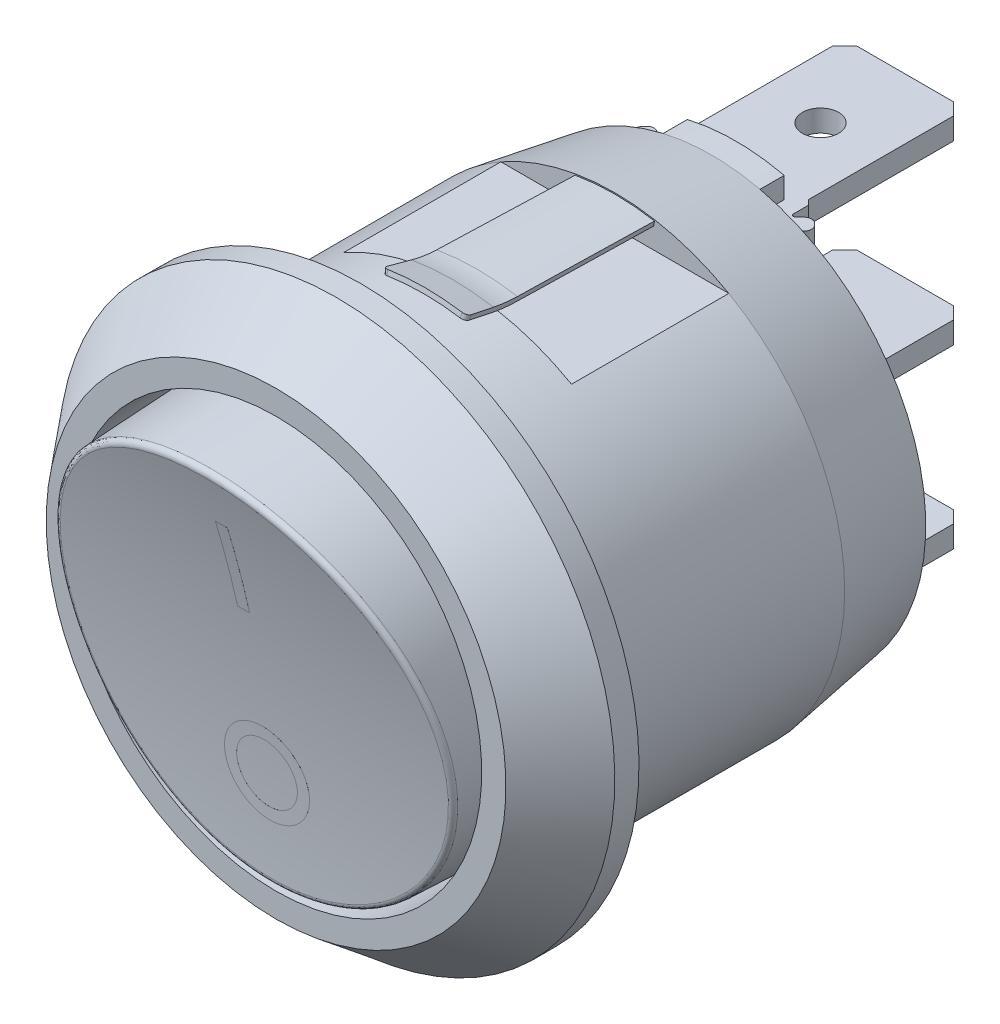
SolidWorks part; units mm, degrees
material "PE Baixa/Média Densidade"
ref_plane "Plano frontal" through (0, 0, 0) normal (0, 0, 1) x (1, 0, 0)
ref_plane "Plano superior" through (0, 0, 0) normal (0, 1, 0) x (1, 0, 0)
ref_plane "Plano direito" through (0, 0, 0) normal (1, 0, 0) x (0, 0, -1)
sketch "Esboço1" plane through (0, 0, 0) normal (1, 0, 0) x (0, 0, -1)
  line L0 (0, 0) -> (-18, 0) construction
  line L1 (0, 0) -> (0, 8.85)
  line L2 (0, 8.85) -> (-4, 9.5)
  line L3 (-4, 9.5) -> (-14.5, 9.5)
  line L4 (-14.5, 9.5) -> (-14.5, 11.5)
  line L5 (-14.5, 11.5) -> (-15.5, 11.5)
  line L6 (-15.5, 11.5) -> (-18, 9.5)
  line L7 (-18, 9.5) -> (-18, 8.5)
  line L8 (-18, 8.5) -> (-12.5, 8.5)
  line L9 (-12.5, 8.5) -> (-12.5, 0)
  line L10 (0, 0) -> (-12.5, 0)
  dimension "D1" = 18
  dimension "D2" = 17.7
  dimension "D3" = 14.5
  dimension "D4" = 19
  dimension "D5" = 4
  dimension "D6" = 23
  dimension "D7" = 1
  dimension "D8" = 17
  dimension "D9" = 5.5
revolve "Revolução1" add sketch "Esboço1" angle 360 about L0
sketch "Esboço2" plane through (0, 0, 0) normal (1, 0, 0) x (0, 0, -1)
  line L0 (-18, 0) -> (0, 0) construction
  line L1 (-18, 9.5) -> (-18, -9.5) construction
  line L2 (-12.6, 0) -> (-12.6, 8.4)
  line L3 (-12.6, 8.4) -> (-21, 8.4) construction
  line L4 (-21, 8) -> (-21, 0)
  line L5 (-12.5, 8.5) -> (-12.5, -8.5) construction
  line L6 (-12.5, 8.5) -> (-18, 8.5) construction
  line L7 (-12.6, 8.4) -> (-21, 8)
  line L8 (-21, 8.4) -> (-21, 8) construction
  line L9 (-12.6, 0) -> (-21, 0)
  dimension "D1" = 0.1
  dimension "D2" = 0.1
  dimension "D3" = 0.4
  dimension "D4" = 3
revolve "Revolução2" add sketch "Esboço2" angle 360 about L9
sketch "Esboço3" plane through (0, 0, 0) normal (1, 0, 0) x (0, 0, -1)
  line L0 (-21, -8) -> (-12.6, -8.4) construction
  line L1 (-21, 8) -> (-24.6303, 8)
  line L2 (-24.6303, 8) -> (-24.6303, -8.1333)
  line L3 (-24.6303, -8.1333) -> (-18.2, -8.1333)
  line L4 (-18.2, -8.1333) -> (-18.2, 9.4452) construction
  line L5 (-18, 9.5) -> (-18, -9.5) construction
  arc A0 (-21, 8) -> (-18.2, -8.1333) centre (-66.0794, -8.1333) cw
  dimension "D1" = 0.2
extrude "Corte-extrusão1" cut sketch "Esboço3" against normal mid plane 30
fillet "Filete1" radius 0.2 1 edges at (4.4558, 6.6703, 20.546)
ref_plane "Plano1" through (0, 0, 24.4108) normal (0, 0, 1) x (1, 0, 0)
surface "Superfície-Offset1" parameters "D1"=0.001
sketch "Esboço4" plane through (0, 0, 24.4108) normal (0, 0, 1) x (1, 0, 0)
  line L0 (-9.5, 0) -> (9.5, 0) construction
  line L1 (0, 0) -> (0, -4.0712) construction
  line L2 (0, -8.1424) -> (0, -4.0712) construction
  line L3 (0, 2.2564) -> (0, 0) construction
  line L4 (-0.25, 5.7564) -> (0.25, 5.7564)
  line L5 (-0.25, 5.7564) -> (-0.25, 2.2564)
  line L6 (-0.25, 2.2564) -> (0.25, 2.2564)
  line L7 (0.25, 5.7564) -> (0.25, 2.2564)
  line L8 (-0.25, 5.7564) -> (0.25, 2.2564) construction
  line L9 (-0.25, 2.2564) -> (0.25, 5.7564) construction
  line L10 (0, 8.0128) -> (0, 5.7564) construction
  circle A0 centre (0, 0) radius 9.5 construction
  circle A1 centre (0, -4.0712) radius 1.75
  circle A2 centre (0, -4.0712) radius 1.25
  spline S0 degree 3 poles (-6.2452, -5.2454) (-5.5004, -6.0245) (-5.0951, -6.3713) (-4.4399, -6.8293) (-4.2136, -6.9715) (-3.7446, -7.2346) (-3.5031, -7.3546) (-2.7693, -7.6754) (-2.2636, -7.8396) (-1.4801, -8.0112) (-1.2132, -8.0559) (-0.6804, -8.1183) (-0.4142, -8.1362) (0.3837, -8.1507) (0.9149, -8.1087) (1.9756, -7.9174) (2.4892, -7.7707) (3.2316, -7.478) (3.4746, -7.3682) (3.9514, -7.1236) (4.1859, -6.9882) (4.8603, -6.5528) (5.2764, -6.2217) (5.8507, -5.6643) (6.0346, -5.4674) (6.3811, -5.0568) (6.5427, -4.8445) (6.994, -4.1873) (7.2503, -3.7225) (7.566, -2.9842) (7.6591, -2.7325) (7.8183, -2.2264) (7.9516, -1.7155) (8.0342, -1.1948) (8.0912, -0.6694) (8.1069, -0.4027) (8.1142, 0.3918) (8.0672, 0.913) (7.922, 1.683) (7.8611, 1.9377) (7.7137, 2.4429) (7.6273, 2.6925) (7.3354, 3.4196) (7.0961, 3.8807) (6.5283, 4.7562) (6.1978, 5.1713) (5.4672, 5.9245) (5.0608, 6.269) (4.1959, 6.8677) (3.7366, 7.124) (3.0056, 7.4423) (2.754, 7.5375) (2.2474, 7.701) (1.7348, 7.8391) (1.2104, 7.9268) (0.68, 7.9888) (0.4102, 8.0069) (-0.3949, 8.0209) (-0.9246, 7.9776) (-1.9703, 7.7887) (-2.4915, 7.6403) (-3.4759, 7.2524) (-3.9436, 7.0131) (-4.6092, 6.5868) (-4.8261, 6.4323) (-5.2401, 6.1061) (-5.4374, 5.9342) (-6.0018, 5.3929) (-6.3413, 4.9981) (-6.7945, 4.3533) (-6.9352, 4.1308) (-7.1922, 3.677) (-7.4262, 3.2125) (-7.6148, 2.7267) (-7.7801, 2.2301) (-7.8515, 1.9749) (-8.0263, 1.2053) (-8.0918, 0.6862) (-8.1212, -0.3642) (-8.0835, -0.9002) (-7.9054, -1.9414) (-7.7661, -2.4509) (-7.4793, -3.1981) (-7.3703, -3.4446) (-7.1308, -3.9207) (-6.9999, -4.1516) (-6.5741, -4.8237) (-6.2452, -5.2454) (-5.5004, -6.0245) (-5.0951, -6.3713) knots -0.03125 -0.03125 0 0 0.03125 0.03125 0.046875 0.046875 0.0625 0.0625 0.09375 0.09375 0.109375 0.109375 0.125 0.125 0.15625 0.15625 0.1875 0.1875 0.203125 0.203125 0.21875 0.21875 0.25 0.25 0.265625 0.265625 0.28125 0.28125 0.3125 0.3125 0.328125 0.328125 0.34375 0.359375 0.359375 0.375 0.375 0.40625 0.40625 0.421875 0.421875 0.4375 0.4375 0.46875 0.46875 0.5 0.5 0.53125 0.53125 0.5625 0.5625 0.578125 0.578125 0.59375 0.609375 0.609375 0.625 0.625 0.65625 0.65625 0.6875 0.6875 0.71875 0.71875 0.734375 0.734375 0.75 0.75 0.78125 0.78125 0.796875 0.796875 0.8125 0.828125 0.828125 0.84375 0.84375 0.875 0.875 0.90625 0.90625 0.9375 0.9375 0.953125 0.953125 0.96875 0.96875 1 1 1.03125 1.03125 1.046875 only from (-5.8728, -5.6349) to (-5.8728, -5.6349) construction
  point P12 (0, 4.0064)
  dimension "D1" = 3.5
  dimension "D3" = 0.5
  dimension "D4" = 3.5
  dimension "D2" = 0.5
extrude "Ressalto-extrusão1" add sketch "Esboço4" against normal up to surface (6.0382 mm away) up to face at (5.0218, 5.9632, 20.3222)
other "Corte de superfície1" flip cut yes
sketch "Esboço5" plane through (0, 0, 0) normal (1, 0, 0) x (0, 0, -1)
  line L0 (-4, 8.25) -> (-4, -8.25) construction
  line L1 (-10.5, 11.4584) -> (-4, 11.4584)
  line L2 (-10.5, 11.4584) -> (-10.5, 8.25)
  line L3 (-10.5, 8.25) -> (-4, 8.25)
  line L4 (-4, 11.4584) -> (-4, 8.25)
  line L5 (-10.5, -11.4584) -> (-4, -11.4584)
  line L6 (-10.5, -11.4584) -> (-10.5, -8.25)
  line L7 (-10.5, -8.25) -> (-4, -8.25)
  line L8 (-4, -11.4584) -> (-4, -8.25)
  line L9 (0, 0) -> (-4, 0) construction
  line L10 (-4, 9.5) -> (-4, -9.5) construction
  dimension "D1" = 16.5
  dimension "D2" = 6.5
extrude "Corte-extrusão2" cut sketch "Esboço5" against normal mid plane 50
sketch "Esboço6" plane through (0, 0, 0) normal (1, 0, 0) x (0, 0, -1)
  line L0 (-4, 9.25) -> (-9.6985, 9.4121)
  line L2 (-4, 9.5) -> (-4, 8.25) construction
  line L3 (-10.7572, 9.5565) -> (-11.9, 9.8393)
  line L4 (-14.5, -11.5) -> (-14.5, 11.5) construction
  line L5 (-10.5, 8.25) -> (-4, 8.25) construction
  line L6 (-3.9943, 9.4499) -> (-9.6928, 9.6121)
  line L7 (-10.7092, 9.7506) -> (-11.852, 10.0334)
  line L8 (-11.852, 10.0334) -> (-11.9, 9.8393)
  line L9 (-3.9943, 9.4499) -> (-4, 9.25)
  line L10 (-4, 0) -> (-9.0622, 0) construction
  line L11 (-4, 8.25) -> (-4, -8.25) construction
  arc A0 (-9.6985, 9.4121) -> (-10.7572, 9.5565) centre (-9.5562, 14.4101) cw
  arc A1 (-9.6928, 9.6121) -> (-10.7092, 9.7506) centre (-9.5562, 14.4101) cw
  dimension "D2" = 5
  dimension "D1" = 2.6
  dimension "D3" = 1
  dimension "D4" = 0.2
revolve "Revolução4" add sketch "Esboço6" angle 20 mid plane about L10
fillet "Filete2" radius 0.2 2 edges at (-1.7254, 9.7854, 11.876) (1.7254, 9.7854, 11.876)
mirror "Espelhar1" about plane through (0, 0, 0) normal (0, 1, 0) of bodies 109
sketch "Esboço7" plane through (0, 0, 4) normal (0, 0, 1) x (1, 0, 0)
  line L0 (-9.4472, 1) -> (-10.4472, 1)
  line L1 (-10.4472, 1) -> (-10.4472, -1)
  line L2 (-10.4472, -1) -> (-9.4472, -1)
  circle A0 centre (0, 0) radius 9.5 construction
  arc A1 (-9.4472, 1) -> (-9.4472, -1) centre (0, 0) ccw
  dimension "D1" = 1
  dimension "D2" = 2
extrude "Ressalto-extrusão2" add sketch "Esboço7" along normal up to surface (10.5 mm away) up to face at (0, 11.5, 14.5)
sketch "Esboço8" plane through (0, 0, 0) normal (0, 0, -1) x (-1, 0, 0)
  line L0 (-2, 8.621) -> (-2, 7.75)
  line L1 (-2, 7.75) -> (2, 7.75)
  line L2 (2, 7.75) -> (2, 8.621)
  line L3 (0, 7.75) -> (0, 8.85) construction
  line L4 (-2, 6.85) -> (2, 6.85)
  line L5 (-2, 6.85) -> (-2, 5.75)
  line L6 (-2, 5.75) -> (2, 5.75)
  line L7 (2, 6.85) -> (2, 5.75)
  line L8 (0, 6.85) -> (0, 5.75) construction
  line L9 (0, -0.45) -> (0, 0.45) construction
  line L10 (-2, 1.55) -> (2, 1.55)
  line L11 (-2, 1.55) -> (-2, 0.45)
  line L12 (-2, 0.45) -> (2, 0.45)
  line L13 (2, 1.55) -> (2, 0.45)
  line L14 (-2, -0.45) -> (2, -0.45)
  line L15 (-2, -0.45) -> (-2, -1.55)
  line L16 (-2, -1.55) -> (2, -1.55)
  line L17 (2, -0.45) -> (2, -1.55)
  line L18 (0, 0) -> (8.85, 0) construction
  line L19 (2, -7.75) -> (2, -8.621)
  line L20 (-2, -8.621) -> (-2, -7.75)
  line L21 (-2, -7.75) -> (2, -7.75)
  line L22 (-2, -6.85) -> (-2, -5.75)
  line L23 (-2, -6.85) -> (2, -6.85)
  line L24 (2, -6.85) -> (2, -5.75)
  line L25 (-2, -5.75) -> (2, -5.75)
  circle A0 centre (0, 0) radius 8.85 construction
  arc A1 (2, 8.621) -> (-2, 8.621) centre (0, 0) ccw
  arc A2 (2, -8.621) -> (-2, -8.621) centre (0, 0) cw
  dimension "D1" = 4
  dimension "D2" = 0.9
  dimension "D3" = 3.1
  dimension "D4" = 0.9
extrude "Ressalto-extrusão3" add sketch "Esboço8" along normal blind 1
sketch "Esboço9" plane through (0, -7.75, 0) normal (0, 1, 0) x (1, 0, 0)
  line L0 (2, 0) -> (3.245, 0)
  line L1 (8.85, 0) -> (2, 0) construction
  line L2 (3.245, 0) -> (3.5379, 0.2929)
  line L3 (3.5379, 0.7172) -> (3.4672, 0.7879)
  line L4 (3.0429, 0.7879) -> (2.8707, 0.6157)
  line L5 (2.7, 0.6864) -> (2.7, 1.3)
  line L6 (2.7, 1.3) -> (2.5, 1.5)
  line L7 (2.5, 1.5) -> (2.5, 7.5)
  line L8 (2.5, 7.5) -> (2, 8)
  line L9 (2, 8) -> (-2, 8)
  line L10 (0, 8) -> (0, 0) construction
  line L11 (-2, 0) -> (2, 0) construction
  line L12 (2, 1) -> (-2, 1) construction
  line L13 (-2, 0) -> (-8.85, 0) construction
  line L14 (-2.5, 7.5) -> (-2, 8)
  line L15 (-2.5, 1.5) -> (-2.5, 7.5)
  line L16 (-2.7, 1.3) -> (-2.5, 1.5)
  line L17 (-2.7, 0.6864) -> (-2.7, 1.3)
  line L18 (-3.0429, 0.7879) -> (-2.8707, 0.6157)
  line L19 (-3.5379, 0.7172) -> (-3.4672, 0.7879)
  line L20 (-3.245, 0) -> (-3.5379, 0.2929)
  line L21 (-2, 0) -> (-3.245, 0)
  line L22 (-2, 0) -> (2, 0)
  arc A0 (3.5379, 0.7172) -> (3.5379, 0.2929) centre (3.3257, 0.505) cw
  arc A1 (3.4672, 0.7879) -> (3.0429, 0.7879) centre (3.255, 0.5757) ccw
  arc A2 (2.7, 0.6864) -> (2.8707, 0.6157) centre (2.8, 0.6864) ccw
  arc A3 (-2.7, 0.6864) -> (-2.8707, 0.6157) centre (-2.8, 0.6864) cw
  arc A4 (-3.4672, 0.7879) -> (-3.0429, 0.7879) centre (-3.255, 0.5757) cw
  arc A5 (-3.5379, 0.7172) -> (-3.5379, 0.2929) centre (-3.3257, 0.505) ccw
  point P20 (3.75, 0.505)
  point P23 (3.255, 1)
  dimension "D9" = 0.3
  dimension "D10" = 0.1
  dimension "D1" = 7.5
  dimension "D2" = 45
  dimension "D3" = 5
  dimension "D4" = 0.2
  dimension "D5" = 45
  dimension "D6" = 0.5
  dimension "D7" = 1.5
  dimension "D8" = 0.7
  dimension "D11" = 8
extrude "Ressalto-extrusão4" add sketch "Esboço9" along normal up to surface (0.9 mm away) separate body up to face at (0, -6.85, -0.5)
sketch "Esboço10" plane through (0, -6.85, 0) normal (0, 1, 0) x (1, 0, 0)
  line L0 (0, 8) -> (0, 4.5) construction
  line L1 (2, 8) -> (-2, 8) construction
  circle A0 centre (0, 4.5) radius 0.75
  dimension "D1" = 3.5
  dimension "D2" = 1.5
extrude "Corte-extrusão3" cut sketch "Esboço10" against normal blind 1
pattern_linear "Padrão linear4" count 3 spacing 7.3 along (0, 1, 0) of bodies 114
